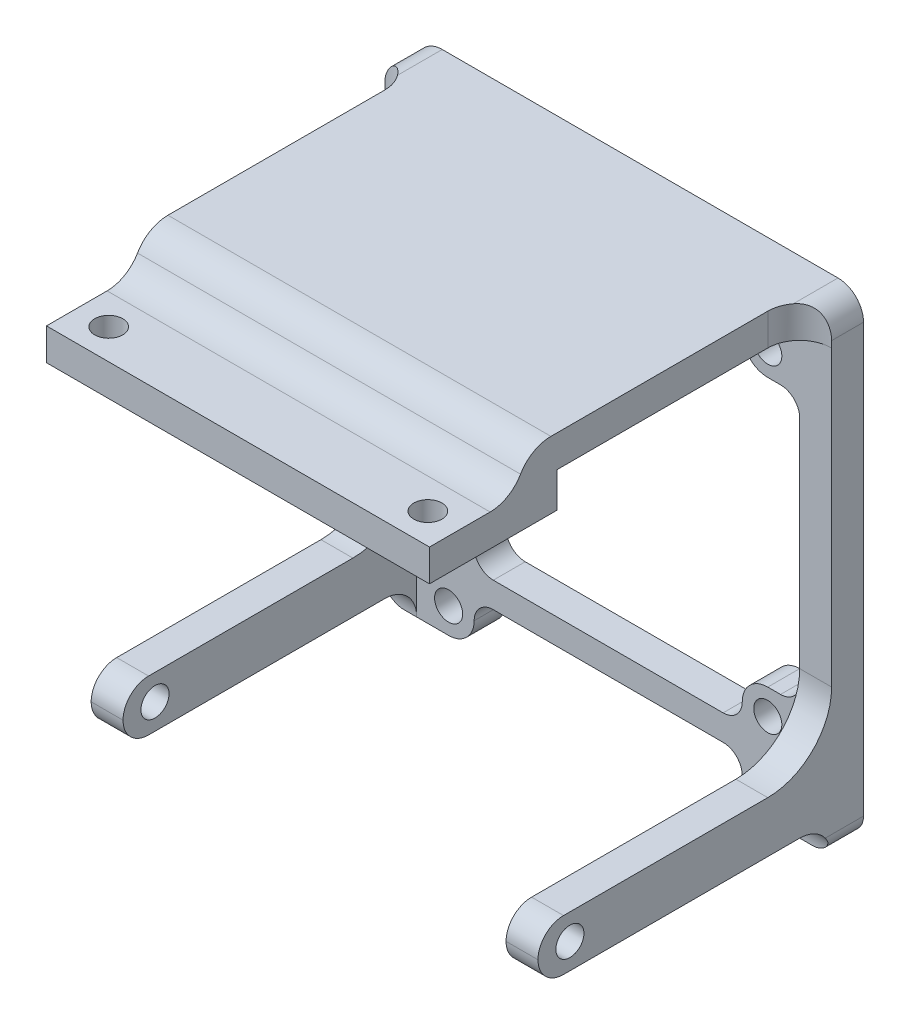
SolidWorks part; units mm, degrees
ref_plane "Front Plane" through (0, 0, 0) normal (0, 0, 1) x (1, 0, 0)
ref_plane "Top Plane" through (0, 0, 0) normal (0, 1, 0) x (1, 0, 0)
ref_plane "Right Plane" through (0, 0, 0) normal (1, 0, 0) x (0, 0, -1)
sketch "Sketch1" plane through (0, 0, 0) normal (0, 0, 1) x (1, 0, 0)
  line L0 (-45.5, 87.8) -> (-45.5, 90.8)
  line L1 (-87.5, 87.8) -> (-45.5, 87.8)
  line L4 (-91.5, 136.8) -> (-96.5, 136.8)
  line L5 (-45.5, 83.8) -> (-45.5, 80.8)
  line L8 (-96.5, 76.8) -> (-101.5, 76.8)
  line L10 (-36.5, 145.8) -> (-41.5, 145.8) construction
  line L12 (-45.5, 145.8) -> (-36.5, 145.8)
  line L13 (-41.5, 136.8) -> (-36.5, 136.8)
  line L14 (-45.5, 140.8) -> (-45.5, 145.8)
  line L16 (-96.5, 145.8) -> (-87.5, 145.8)
  line L17 (-101.5, 76.8) -> (-101.5, 145.8)
  line L21 (-41.5, 94.8) -> (-36.5, 94.8)
  line L26 (-91.5, 94.8) -> (-96.5, 94.8)
  line L28 (-45.5, 83.8) -> (-87.5, 83.8)
  line L29 (-87.5, 83.8) -> (-87.5, 80.8)
  line L30 (-87.5, 87.8) -> (-87.5, 90.8)
  line L31 (-36.5, 76.8) -> (-31.5, 76.8)
  line L32 (-91.5, 76.8) -> (-96.5, 76.8)
  line L33 (-41.5, 76.8) -> (-36.5, 76.8)
  line L43 (-87.5, 145.8) -> (-87.5, 140.8)
  line L44 (-31.5, 76.8) -> (-31.5, 145.8)
  line L45 (-31.5, 145.8) -> (-36.5, 145.8)
  line L46 (-36.5, 136.8) -> (-36.5, 94.8)
  line L47 (-101.5, 145.8) -> (-96.5, 145.8)
  line L48 (-96.5, 136.8) -> (-96.5, 94.8)
  circle A0 centre (-91.5, 140.8) radius 2.2
  arc A2 (-87.5, 140.8) -> (-91.5, 136.8) centre (-91.5, 140.8) cw
  arc A3 (-45.5, 140.8) -> (-41.5, 136.8) centre (-41.5, 140.8) ccw
  circle A4 centre (-41.5, 140.8) radius 2.2
  circle A5 centre (-41.5, 90.8) radius 2.2
  arc A6 (-45.5, 90.8) -> (-41.5, 94.8) centre (-41.5, 90.8) cw
  arc A7 (-87.5, 90.8) -> (-91.5, 94.8) centre (-91.5, 90.8) ccw
  circle A8 centre (-91.5, 90.8) radius 2.2
  circle A9 centre (-91.5, 80.8) radius 2.2
  arc A10 (-87.5, 80.8) -> (-91.5, 76.8) centre (-91.5, 80.8) cw
  arc A11 (-45.5, 80.8) -> (-41.5, 76.8) centre (-41.5, 80.8) ccw
  circle A12 centre (-41.5, 80.8) radius 2.2
extrude "Boss-Extrude1" add sketch "Sketch1" along normal blind 5
fillet "Fillet1" radius 3 8 edges at (-36.5, 136.8, 2.5) (-96.5, 136.8, 2.5) (-36.5, 94.8, 2.5) (-45.5, 87.8, 2.5) (-45.5, 83.8, 2.5) (-87.5, 83.8, 2.5) (-87.5, 87.8, 2.5) (-96.5, 94.8, 2.5)
fillet "Fillet2" radius 3 2 edges at (-31.5, 76.8, 2.5) (-101.5, 76.8, 2.5)
sketch "Sketch2" plane through (0, 145.8, 0) normal (0, 1, 0) x (1, 0, 0)
  line L0 (-31.5, 0) -> (-31.5, -43)
  line L1 (-31.5, 0) -> (-101.5, 0)
  line L2 (-101.5, 0) -> (-101.5, -43)
  line L3 (-101.5, -43) -> (-31.5, -43)
extrude "Boss-Extrude2" add sketch "Sketch2" along normal blind 5
sketch "Sketch3" plane through (0, 0, 43) normal (0, 0, 1) x (1, 0, 0)
  line L0 (-31.5, 150.8) -> (-31.5, 140.3)
  line L1 (-31.5, 79.8) -> (-31.5, 145.8) construction
  line L2 (-31.5, 140.3) -> (-101.5, 140.3)
  line L3 (-101.5, 145.8) -> (-101.5, 79.8) construction
  line L4 (-101.5, 140.3) -> (-101.5, 150.8)
  line L5 (-101.5, 150.8) -> (-31.5, 150.8)
extrude "Boss-Extrude3" add sketch "Sketch3" along normal blind 5
sketch "Sketch4" plane through (0, 0, 48) normal (0, 0, 1) x (1, 0, 0)
  line L0 (-31.5, 140.3) -> (-31.5, 145.3)
  line L1 (-31.5, 140.3) -> (-31.5, 150.8) construction
  line L5 (-101.5, 140.3) -> (-31.5, 140.3)
  line L6 (-101.5, 140.3) -> (-101.5, 145.3)
  line L7 (-101.5, 150.8) -> (-101.5, 140.3) construction
  line L8 (-101.5, 145.3) -> (-31.5, 145.3)
extrude "Boss-Extrude4" add sketch "Sketch4" along normal blind 15
fillet "Fillet3" radius 5.5 1 edges at (-66.5, 145.3, 48)
sketch "Sketch6" plane through (0, 150.8, 0) normal (0, 1, 0) x (1, 0, 0)
  line L1 (-101.5, 0) -> (-101.5, -48) construction
  line L2 (-101.5, -5) -> (-96.5, -5)
  line L3 (-96.5, -5) -> (-96.5, -63)
  line L4 (-31.5, -63) -> (-101.5, -63) construction
  line L5 (-96.5, -63) -> (-101.5, -63)
  line L6 (-101.5, -63) -> (-101.5, -5)
  line L8 (-31.5, -63) -> (-31.5, -5)
  line L9 (-36.5, -63) -> (-31.5, -63)
  line L10 (-36.5, -5) -> (-36.5, -63)
  line L11 (-31.5, -5) -> (-36.5, -5)
extrude "Cut-Extrude1" cut sketch "Sketch6" against normal blind 15
fillet "Fillet4" radius 5.5 1 edges at (-66.5, 150.8, 48)
fillet "Fillet5" radius 5 2 edges at (-36.5, 148.3, 5) (-96.5, 148.3, 5)
sketch "Sketch7" plane through (0, 145.3, 0) normal (0, 1, 0) x (1, 0, 0)
  circle A0 centre (-91.5, -58.25) radius 2.2
  circle A1 centre (-41.5, -58.25) radius 2.2
extrude "Cut-Extrude2" cut sketch "Sketch7" against normal blind 15
sketch "Sketch8" plane through (0, 0, 5) normal (0, 0, 1) x (1, 0, 0)
  line L1 (-96.5, 81.8) -> (-101.5, 81.8)
  line L2 (-101.5, 145.8) -> (-101.5, 79.8) construction
  line L4 (-101.5, 89.8) -> (-96.5, 89.8)
  line L5 (-96.5, 89.8) -> (-96.5, 81.8)
  line L8 (-101.5, 81.8) -> (-101.5, 89.8)
  line L9 (-36.5, 81.8) -> (-31.5, 81.8)
  line L10 (-36.5, 89.8) -> (-36.5, 81.8)
  line L11 (-31.5, 89.8) -> (-36.5, 89.8)
  line L12 (-31.5, 89.8) -> (-31.5, 81.8)
extrude "Boss-Extrude5" add sketch "Sketch8" along normal blind 46
fillet "Fillet7" radius 10 2 edges at (-99, 89.8, 5) (-34, 89.8, 5)
fillet "Fillet8" radius 3 2 edges at (-87.5, 145.8, 2.5) (-45.5, 145.8, 2.5)
sketch "Sketch9" plane through (-31.5, 0, 0) normal (1, 0, 0) x (0, 0, -1)
fillet "Fillet9" radius 5 2 edges at (-34, 81.8, 5) (-99, 81.8, 5)
sketch "Sketch10" plane through (-101.5, 0, 0) normal (-1, 0, 0) x (0, 0, 1)
  circle A0 centre (46, 85.8) radius 2.2
extrude "Cut-Extrude3" cut sketch "Sketch10" against normal through all
fillet "Fillet10" radius 4 4 edges at (-99, 81.8, 51) (-99, 89.8, 51) (-34, 81.8, 51) (-34, 89.8, 51)
fillet "Fillet11" radius 4 1 edges at (-101.5, 150.8, 2.5)
fillet "Fillet12" radius 4 1 edges at (-31.5, 150.8, 2.5)
